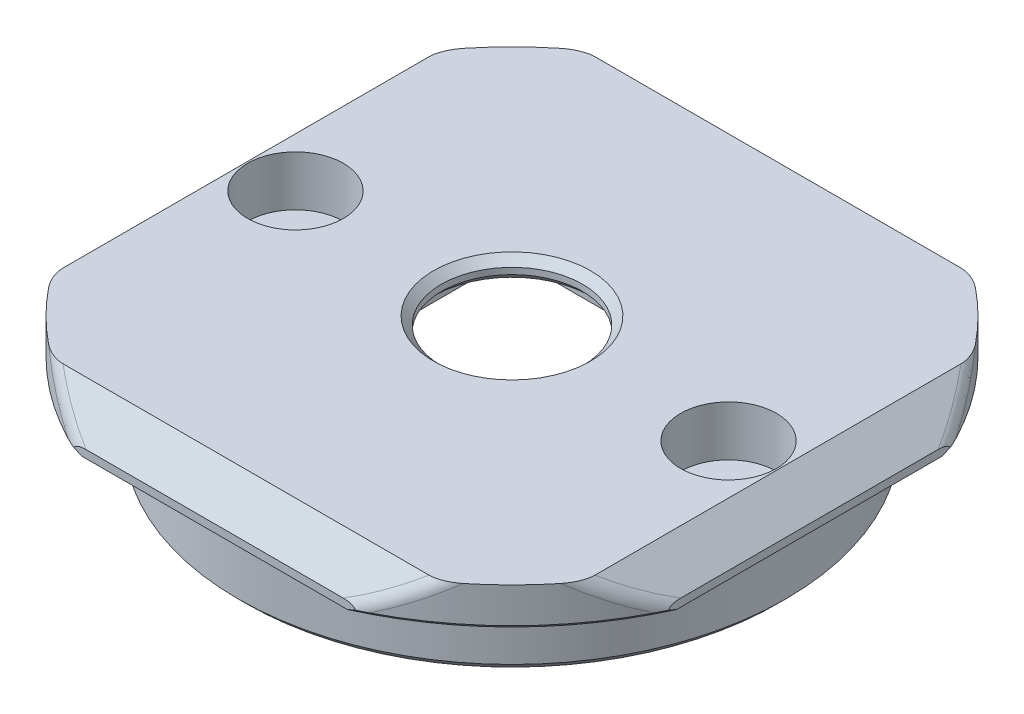
SolidWorks part; units mm, degrees
ref_plane "Front Plane" through (0, 0, 0) normal (0, 0, 1) x (1, 0, 0)
ref_plane "Top Plane" through (0, 0, 0) normal (0, 1, 0) x (1, 0, 0)
ref_plane "Right Plane" through (0, 0, 0) normal (1, 0, 0) x (0, 0, -1)
sketch "Sketch1" plane through (0, 0, 0) normal (0, 1, 0) x (1, 0, 0)
  line L1 (-10.15, -10.15) -> (10.15, -10.15)
  line L2 (-10.15, -10.15) -> (-10.15, 10.15)
  line L3 (-10.15, 10.15) -> (10.15, 10.15)
  line L4 (10.15, -10.15) -> (10.15, 10.15)
  line L5 (-10.15, -10.15) -> (10.15, 10.15) construction
  line L6 (-10.15, 10.15) -> (10.15, -10.15) construction
  circle A0 centre (0, 0) radius 17.45
  point P0 (0, 0)
  point P5 (0, 0)
  dimension "D2" = 34.9
  dimension "D1" = 20.3
extrude "Boss-Extrude1" add sketch "Sketch1" along normal blind 4.9
sketch "Sketch7" plane through (0, 4.9, 0) normal (0, 1, 0) x (1, 0, 0)
  line L1 (-10.15, 10.15) -> (10.15, 10.15)
  line L2 (-10.15, 10.15) -> (-10.15, -10.15)
  line L3 (-10.15, -10.15) -> (10.15, -10.15)
  line L4 (10.15, 10.15) -> (10.15, -10.15)
  circle A0 centre (0, 0) radius 21
  dimension "D1" = 42
extrude "Boss-Extrude5" add sketch "Sketch7" along normal blind 0.5
sketch "Sketch6" plane through (0, 5.4, 0) normal (0, 1, 0) x (1, 0, 0)
  line L1 (-10.15, 10.15) -> (10.15, 10.15)
  line L2 (-10.15, 10.15) -> (-10.15, -10.15)
  line L3 (-10.15, -10.15) -> (10.15, -10.15)
  line L4 (10.15, 10.15) -> (10.15, -10.15)
  line L5 (-16.95, -16.95) -> (16.95, -16.95)
  line L6 (-16.95, -16.95) -> (-16.95, 16.95)
  line L7 (-16.95, 16.95) -> (16.95, 16.95)
  line L8 (16.95, -16.95) -> (16.95, 16.95)
  line L9 (-16.95, -16.95) -> (16.95, 16.95) construction
  line L10 (-16.95, 16.95) -> (16.95, -16.95) construction
  point P4 (0, 0)
  dimension "D1" = 6.8
extrude "Boss-Extrude4" add sketch "Sketch6" along normal blind 2
chamfer "Chamfer1" distance 2 angle 45 4 edges at (-16.95, 5.4, 0) (0, 5.4, -16.95) (16.95, 5.4, 0) (0, 5.4, 16.95)
sketch "Sketch9" plane through (0, 7.4, 0) normal (0, 1, 0) x (1, 0, 0)
  line L0 (-9.0497, 18.95) -> (9.0497, 18.95)
  line L1 (9.0497, 18.95) -> (18.95, 18.95) construction
  line L2 (18.95, 18.95) -> (18.95, 9.0497) construction
  line L3 (18.95, 9.0497) -> (18.95, -9.0497)
  line L4 (18.95, -9.0497) -> (18.95, -18.95) construction
  line L5 (18.95, -18.95) -> (9.0497, -18.95) construction
  line L6 (9.0497, -18.95) -> (-9.0497, -18.95)
  line L7 (-9.0497, -18.95) -> (-18.95, -18.95) construction
  line L8 (-18.95, -18.95) -> (-18.95, -9.0497) construction
  line L9 (-18.95, -9.0497) -> (-18.95, 9.0497)
  line L10 (-18.95, 9.0497) -> (-18.95, 18.95) construction
  line L11 (-18.95, 18.95) -> (-9.0497, 18.95) construction
  line L13 (-26.7487, 26.8068) -> (29.3423, 26.8068)
  line L14 (-26.7487, 26.8068) -> (-26.7487, -29.5939)
  line L15 (-26.7487, -29.5939) -> (29.3423, -29.5939)
  line L16 (29.3423, 26.8068) -> (29.3423, -29.5939)
  arc A0 (-18.95, -9.0497) -> (-9.0497, -18.95) centre (0, 0) ccw
  arc A1 (-18.95, 9.0497) -> (-18.95, -9.0497) centre (0, 0) ccw construction
  arc A2 (9.0497, 18.95) -> (-9.0497, 18.95) centre (0, 0) ccw construction
  arc A3 (-9.0497, 18.95) -> (-18.95, 9.0497) centre (0, 0) ccw
  arc A4 (18.95, -9.0497) -> (18.95, 9.0497) centre (0, 0) ccw construction
  arc A5 (18.95, 9.0497) -> (9.0497, 18.95) centre (0, 0) ccw
  arc A6 (-9.0497, -18.95) -> (9.0497, -18.95) centre (0, 0) ccw construction
  arc A7 (9.0497, -18.95) -> (18.95, -9.0497) centre (0, 0) ccw
extrude "Cut-Extrude7" cut sketch "Sketch9" against normal through all
sketch "Sketch10" plane through (0, 0, 0) normal (0, -1, 0) x (1, 0, 0)
  line L0 (10.15, 0) -> (17.45, 0) construction
  line L2 (0, 0) -> (10.15, 0) construction
  line L3 (10.15, 10.15) -> (10.15, -10.15) construction
  line L4 (0, 0) -> (0, 10.15) construction
  line L5 (-10.15, 10.15) -> (10.15, 10.15) construction
  circle A0 centre (0, 0) radius 17.45 construction
  circle A1 centre (13.8, 0) radius 1.8
  circle A3 centre (-13.8, 0) radius 1.8
  circle A4 centre (13.8, 0) radius 3.05
  circle A5 centre (-13.8, 0) radius 3.05
  dimension "D1" = 3.6
  dimension "D2" = 6.1
extrude "Cut-Extrude8" cut sketch "Sketch10" against normal through all contours A3 | A1 region at (13.8, 0, 0) region at (-13.8, 0, 0)
extrude "Cut-Extrude9" cut sketch "Sketch10<3>" against normal blind 10 from offset 4.2 offset against normal yes
sketch "Sketch10<3>" plane through (0, 0, 0) normal (0, -1, 0) x (1, 0, 0) same geometry as "Sketch10"
extrude "Boss-Extrude6" add sketch "Sketch10<4>" along normal blind 0.2 from surface contours A1 | A3 region at (13.8, 0, 0) region at (-13.8, 0, 0) starting at face at (13.8, 4.2, -1.8)
sketch "Sketch10<4>" plane through (0, 0, 0) normal (0, -1, 0) x (1, 0, 0) same geometry as "Sketch10"
sketch "Sketch11" plane through (0, 7.4, 0) normal (0, 1, 0) x (1, 0, 0)
  line L1 (-10.15, 10.15) -> (10.15, 10.15)
  line L2 (-10.15, 10.15) -> (-10.15, -10.15)
  line L3 (-10.15, -10.15) -> (10.15, -10.15)
  line L4 (10.15, 10.15) -> (10.15, -10.15)
  circle A0 centre (0, 0) radius 4.5
  dimension "D1" = 9
extrude "Boss-Extrude7" add sketch "Sketch11" against normal blind 1.4
chamfer "Chamfer3" distance 0.25 angle 45 4 edges at (-14.8492, 4.9, -14.8492) (14.8492, 4.9, -14.8492) (14.8492, 4.9, 14.8492) (-14.8492, 4.9, 14.8492)
chamfer "Chamfer4" distance 0.5 angle 45 9 edges at (0, 0, 10.15) (-10.15, 0, 0) (0, 0, -10.15) (10.15, 0, 0) (0, 0, 17.45) (13.8, 0, -1.8) (-13.8, 0, -1.8) (0, 7.4, 4.5) (0, 6, 4.5)
fillet "Fillet1" radius 1 8 edges at (18.0279, 6.3221, 10.7701) (10.7701, 6.3221, 18.0279) (18.0279, 6.3221, -10.7701) (10.7701, 6.3221, -18.0279) (-10.7701, 6.3221, -18.0279) (-18.0279, 6.3221, -10.7701) (-18.0279, 6.3221, 10.7701) (-10.7701, 6.3221, 18.0279)
